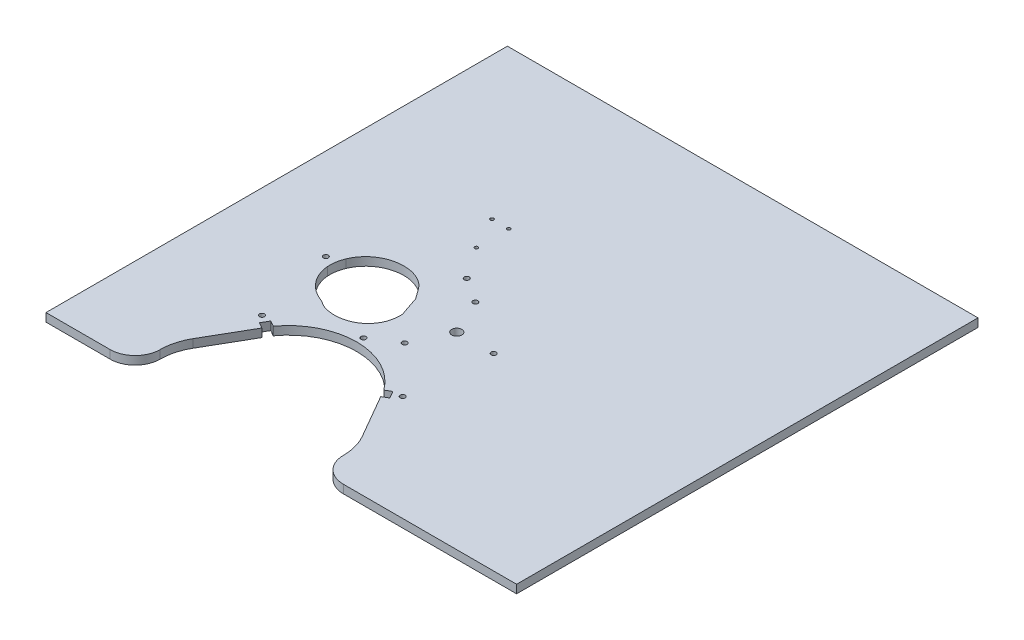
SolidWorks part; units mm, degrees
material "ABS PC"
ref_plane "Plan de face" through (0, 0, 0) normal (0, 0, 1) x (1, 0, 0)
ref_plane "Plan de dessus" through (0, 0, 0) normal (0, 1, 0) x (1, 0, 0)
ref_plane "Plan de droite" through (0, 0, 0) normal (1, 0, 0) x (0, 0, -1)
sketch "Esquisse1" plane through (0, 0, 0) normal (0, 1, 0) x (1, 0, 0)
  line L1 (-140.5, 31.9) -> (141.9979, 31.9)
  line L2 (-140.5, 31.9) -> (-140.5, -245.0829)
  line L3 (-140.5, -245.0829) -> (141.9979, -245.0829)
  line L4 (141.9979, 31.9) -> (141.9979, -245.0829)
  line L5 (38, -245.0829) -> (54.7016, -245.0829) construction
  line L6 (99.5, 31.9) -> (113.5, 31.9) construction
  arc A0 (-32, -23.5) -> (-95.029, -220.3153) centre (-32, -132) ccw construction
extrude "Boss.-Extru.1" add sketch "Esquisse1" along normal blind 5
sketch "Esquisse2" plane through (0, 0, 0) normal (0, 1, 0) x (1, 0, 0)
  line L3 (-65.1815, -184) -> (-68.6457, -182)
  line L4 (-68.6457, -182) -> (-71.1457, -186.3301)
  line L5 (-71.1457, -186.3301) -> (-67.6815, -188.3301)
  line L7 (-32, -132) -> (-32, -245.0829) construction
  line L8 (-65.1815, -184) -> (-67.6815, -188.3301) construction
  line L9 (-62.6323, -132) -> (62.6323, -132) construction
  line L10 (-32, -62.6323) -> (-32, 62.6323) construction
  line L11 (-67.6815, -188.3301) -> (-82.8539, -214.6094)
  line L13 (-65.1815, -184) -> (-61.7174, -186) construction
  line L14 (-32, -168.5125) -> (-32, -231.5125) construction
  line L16 (140.1, -245.0829) -> (-140.1, -245.0829) construction
  line L17 (-140.5, -245.0829) -> (141.9979, -245.0829) construction
  line L18 (1.1815, -184) -> (-2.2826, -186) construction
  line L20 (1.1815, -184) -> (3.6815, -188.3301) construction
  line L21 (3.6815, -188.3301) -> (18.8539, -214.6094)
  line L22 (7.1457, -186.3301) -> (3.6815, -188.3301)
  line L23 (4.6457, -182) -> (7.1457, -186.3301)
  line L24 (1.1815, -184) -> (4.6457, -182)
  line L25 (-69.8957, -184.1651) -> (-74.2258, -181.6651) construction
  line L26 (-102, -245.0829) -> (38, -245.0829)
  arc A1 (1.1815, -184) -> (-65.1815, -184) centre (-32, -208.0829) ccw
  arc A2 (-102, -245.0829) -> (-87, -230.0829) centre (-102, -230.0829) ccw
  arc A3 (-102, -245.0829) -> (-93.2863, -217.8734) centre (-102, -230.0829) ccw construction
  arc A4 (-87, -230.0829) -> (-82.8539, -214.6094) centre (-56.0531, -230.0829) cw
  arc A5 (23, -230.0829) -> (18.8539, -214.6094) centre (-7.9469, -230.0829) ccw
  arc A6 (38, -245.0829) -> (23, -230.0829) centre (38, -230.0829) cw
  circle A8 centre (-74.2258, -181.6651) radius 1.5
  circle A10 centre (10.2258, -181.6651) radius 1.5
  dimension "D4" = 41
  dimension "D8" = 5
  dimension "D9" = 3
  dimension "D1" = 4
  dimension "D2" = 52
  dimension "D3" = 37
  dimension "D5" = 90
  dimension "D6" = 5
  dimension "D7" = 30
extrude "Enlèv. mat.-Extru.2" cut sketch "Esquisse2" along normal through all
sketch "Esquisse3" plane through (0, 5, 0) normal (0, 1, 0) x (1, 0, 0)
  line L0 (-34.1228, -139.1933) -> (-38.0727, -127.5986) construction
  line L1 (-32.6381, -138.8997) -> (-36.7122, -126.9407)
  spline S0 degree 3 poles (622.8385, 1730.6752) (80.7611, -245.6058) (-80.6273, -179.6704) (-78.4184, -133.519) (-78.3402, -132.7796) (-78.0993, -131.3086) (-77.9355, -130.5788) (-42.7423, -7.2308) (1168.5437, -237.6426) (1911.2991, -327.4332) knots -15.02078 -15.02078 -15.02078 -15.02078 0.25 0.25 0.5 0.5 0.75 0.75 43.632511 43.632511 43.632511 43.632511 only from (-78.4282, -136.5) to (-77, -127.755)
  spline S1 degree 3 poles (-2047.8331, 22.2373) (1285.2883, 298.7745) (-111.0384, -8.8099) (-77.7521, -140.3949) (-77.5862, -140.9451) (-77.2098, -142.0199) (-76.9992, -142.5463) (-76.3026, -144.0933) (-75.7516, -145.082) (-74.8018, -146.5043) (-74.4641, -146.9675) (-73.7589, -147.8582) (-73.3897, -148.2875) (-72.6207, -149.1162) (-72.221, -149.5157) (-71.3904, -150.2844) (-70.9598, -150.6538) (-70.0613, -151.3565) (-69.5957, -151.6914) (-68.8865, -152.1695) (-68.6478, -152.325) (-68.1687, -152.6332) (-67.9269, -152.7834) (-67.1868, -153.2096) (-66.681, -153.4729) (-65.648, -153.9633) (-65.1207, -154.1899) (-64.0641, -154.6374) (-63.5349, -154.8594) (-62.7536, -155.2167) (-62.5025, -155.3541) (-50.6518, -163.0047) (-54.4985, -200.5995) (887.4578, 1603.7366) knots -14.73487 -14.73487 -14.73487 -14.73487 0.125 0.125 0.1875 0.1875 0.25 0.25 0.375 0.375 0.4375 0.4375 0.5 0.5 0.5625 0.5625 0.625 0.625 0.6875 0.6875 0.71875 0.71875 0.75 0.75 0.8125 0.8125 0.875 0.875 0.9375 0.9375 0.96875 0.96875 2.47079 2.47079 2.47079 2.47079 only from (-78.4282, -136.5) to (-61.5478, -156)
  spline S2 degree 3 poles (-1745.4139, 892.0598) (133.9741, 43.0874) (-4.0887, -175.9233) (-59.26, -157.2053) (-59.4819, -157.1257) (-59.8129, -157.0004) (-59.9231, -156.9582) (-60.1393, -156.8624) (-60.2451, -156.8096) (-60.557, -156.6406) (-60.7605, -156.5209) (-73.1987, -148.6858) (-65.0496, -108.9252) (-1170.5294, -1819.9055) knots -30.265211 -30.265211 -30.265211 -30.265211 0.5 0.5 0.625 0.625 0.6875 0.6875 0.75 0.75 0.875 0.875 8.537384 8.537384 8.537384 8.537384 only from (-56.3008, -158) to (-61.5478, -156)
  spline S3 degree 3 poles (-1956.1275, 426.9773) (36.5324, -0.0898) (-5.7039, -154.0463) (-51.2435, -158.3269) (-51.8765, -158.3561) (-53.1445, -158.356) (-53.7811, -158.3264) (-125.6227, -151.5571) (-150.9564, 223.9249) (-22.0957, 1838.9163) knots -17.515041 -17.515041 -17.515041 -17.515041 0.25 0.25 0.5 0.5 0.75 0.75 28.888572 28.888572 28.888572 28.888572 only from (-48.7229, -158) to (-56.3008, -158)
  spline S4 degree 3 poles (-1977.7479, 321.8791) (-6.2878, 50.8205) (-0.115, -141.0202) (-98.7511, -175.969) (-241.4243, 33.4773) (1700.8536, 790.126) knots -23.848551 -23.848551 -23.848551 -23.848551 0.5 0.5 28.682267 28.682267 28.682267 28.682267 only from (-43.0995, -156) to (-48.7229, -158)
  spline S5 degree 3 poles (-1413.2384, 1297.5395) (-406.1116, 94.5412) (-96.3939, -196.3537) (-40.3273, -154.1412) (-39.6978, -153.5933) (-38.8098, -152.698) (-38.5222, -152.3857) (-37.972, -151.7435) (-37.7102, -151.4142) (-36.9651, -150.4011) (-36.5206, -149.6933) (-35.9321, -148.5831) (-35.7493, -148.2047) (-35.4099, -147.4317) (-35.253, -147.0364) (-34.8315, -145.8445) (-34.6116, -145.0363) (-34.2836, -143.3948) (-34.1756, -142.5614) (-29.468, -67.9459) (-444.4271, -29.1967) (1924.0799, 241.8608) knots -10.283304 -10.283304 -10.283304 -10.283304 0.125 0.125 0.25 0.25 0.3125 0.3125 0.375 0.375 0.5 0.5 0.5625 0.5625 0.625 0.625 0.75 0.75 0.875 0.875 11.782868 11.782868 11.782868 11.782868 only from (-43.0995, -156) to (-34.1228, -139.1933)
  spline S6 degree 3 poles (-1551.9542, -1429.2656) (-225.4463, -439.24) (5.2747, -190.2243) (-38.7241, -126.6321) (-38.8938, -126.395) (-39.4011, -125.6828) (-39.7418, -125.2097) (-65.8115, -89.2739) (-97.4387, -57.3229) (-1683.4527, -1262.3111) knots -32.920621 -32.920621 -32.920621 -32.920621 0.125 0.125 0.25 0.25 0.5 0.5 19.284457 19.284457 19.284457 19.284457 only from (-38.0727, -127.5986) to (-42.1803, -121.9365)
  spline S7 degree 3 poles (-1585.122, -1394.0623) (-104.6708, -110.2382) (-59.5313, -102.5716) (-23.2166, -142.8993) (-57.0039, -213.0881) (1509.1144, 1139.2237) knots -20.453469 -20.453469 -20.453469 -20.453469 0.5 0.5 26.410068 26.410068 26.410068 26.410068 only from (-44.5252, -119.3729) to (-42.1803, -121.9365)
  spline S8 degree 3 poles (-2016.7995, 207.9698) (-31.3521, -186.0458) (-27.1415, -132.0896) (-45.8045, -118.3724) (-46.1412, -118.1443) (-47.17, -117.4994) (-47.8823, -117.1198) (-49.3548, -116.4512) (-50.1177, -116.1613) (-51.6655, -115.6765) (-52.453, -115.4795) (-54.8487, -115.0237) (-56.4515, -114.9032) (-58.4616, -114.9674) (-58.864, -114.9913) (-59.6694, -115.0612) (-60.0736, -115.1075) (-61.2787, -115.279) (-62.069, -115.4364) (-63.6237, -115.8348) (-64.3882, -116.0762) (-65.8912, -116.6433) (-66.6307, -116.9704) (-68.8015, -118.081) (-70.1374, -118.9698) (-71.9752, -120.5241) (-72.5597, -121.0797) (-73.6682, -122.2715) (-74.1798, -122.8963) (-75.1225, -124.1965) (-75.5545, -124.8718) (-100.0718, -168.7665) (20.7952, -315.4615) (1850.5018, 377.9945) knots -1.71545 -1.71545 -1.71545 -1.71545 0.03125 0.03125 0.0625 0.0625 0.125 0.125 0.1875 0.1875 0.25 0.25 0.375 0.375 0.40625 0.40625 0.4375 0.4375 0.5 0.5 0.5625 0.5625 0.625 0.625 0.75 0.75 0.8125 0.8125 0.875 0.875 0.9375 0.9375 4.786771 4.786771 4.786771 4.786771 only from (-44.5252, -119.3729) to (-77, -127.755)
  spline S9 degree 3 poles (-44.5252, -119.3729) (-44.8276, -119.1086) (-45.1484, -118.8546) (-45.8045, -118.3724) (-46.1412, -118.1443) (-47.17, -117.4994) (-47.8823, -117.1198) (-49.3548, -116.4512) (-50.1177, -116.1613) (-51.6655, -115.6765) (-52.453, -115.4795) (-54.8487, -115.0237) (-56.4515, -114.9032) (-58.4616, -114.9674) (-58.864, -114.9913) (-59.6694, -115.0612) (-60.0736, -115.1075) (-61.2787, -115.279) (-62.069, -115.4364) (-63.6237, -115.8348) (-64.3882, -116.0762) (-65.8912, -116.6433) (-66.6307, -116.9704) (-68.8015, -118.081) (-70.1374, -118.9698) (-71.9752, -120.5241) (-72.5597, -121.0797) (-73.6682, -122.2715) (-74.1798, -122.8963) (-75.1225, -124.1965) (-75.5545, -124.8718) (-76.3379, -126.2745) (-76.6914, -127.0031) (-77, -127.755) knots 0 0 0 0 0.03125 0.03125 0.0625 0.0625 0.125 0.125 0.1875 0.1875 0.25 0.25 0.375 0.375 0.40625 0.40625 0.4375 0.4375 0.5 0.5 0.5625 0.5625 0.625 0.625 0.75 0.75 0.8125 0.8125 0.875 0.875 0.9375 0.9375 1 1 1 1 construction
  spline S10 degree 3 poles (-44.5252, -119.3729) (-44.0857, -119.7569) (-43.6818, -120.1725) (-42.9069, -121.033) (-42.5395, -121.4811) (-42.1803, -121.9365) knots 0 0 0 0 0.5 0.5 1 1 1 1 construction
  spline S11 degree 3 poles (-38.0727, -127.5986) (-38.2306, -127.3537) (-38.3925, -127.1114) (-38.7241, -126.6321) (-38.8938, -126.395) (-39.4011, -125.6828) (-39.7418, -125.2097) (-40.769, -123.7937) (-41.4579, -122.8522) (-42.1803, -121.9365) knots 0 0 0 0 0.125 0.125 0.25 0.25 0.5 0.5 1 1 1 1 construction
  spline S12 degree 3 poles (-43.0995, -156) (-42.36, -155.596) (-41.658, -155.143) (-40.3273, -154.1412) (-39.6978, -153.5933) (-38.8098, -152.698) (-38.5222, -152.3857) (-37.972, -151.7435) (-37.7102, -151.4142) (-36.9651, -150.4011) (-36.5206, -149.6933) (-35.9321, -148.5831) (-35.7493, -148.2047) (-35.4099, -147.4317) (-35.253, -147.0364) (-34.8315, -145.8445) (-34.6116, -145.0363) (-34.2836, -143.3948) (-34.1756, -142.5614) (-34.069, -140.8707) (-34.0707, -140.0299) (-34.1228, -139.1933) knots 0 0 0 0 0.125 0.125 0.25 0.25 0.3125 0.3125 0.375 0.375 0.5 0.5 0.5625 0.5625 0.625 0.625 0.75 0.75 0.875 0.875 1 1 1 1 construction
  spline S13 degree 3 poles (-43.0995, -156) (-43.978, -156.4799) (-44.895, -156.8867) (-46.7726, -157.552) (-47.7397, -157.8128) (-48.7229, -158) knots 0 0 0 0 0.5 0.5 1 1 1 1 construction
  spline S14 degree 3 poles (-48.7229, -158) (-49.3482, -158.1191) (-49.9796, -158.2081) (-51.2435, -158.3269) (-51.8765, -158.3561) (-53.1445, -158.356) (-53.7811, -158.3264) (-55.0464, -158.2072) (-55.6755, -158.1184) (-56.3008, -158) knots 0 0 0 0 0.25 0.25 0.5 0.5 0.75 0.75 1 1 1 1 construction
  spline S15 degree 3 poles (-56.3008, -158) (-57.2287, -157.8243) (-58.1437, -157.584) (-59.26, -157.2053) (-59.4819, -157.1257) (-59.8129, -157.0004) (-59.9231, -156.9582) (-60.1393, -156.8624) (-60.2451, -156.8096) (-60.557, -156.6406) (-60.7605, -156.5209) (-61.1598, -156.2694) (-61.3541, -156.1351) (-61.5478, -156) knots 0 0 0 0 0.5 0.5 0.625 0.625 0.6875 0.6875 0.75 0.75 0.875 0.875 1 1 1 1 construction
  spline S16 degree 3 poles (-78.4282, -136.5) (-78.3481, -137.6268) (-78.1704, -138.7415) (-77.7521, -140.3949) (-77.5862, -140.9451) (-77.2098, -142.0199) (-76.9992, -142.5463) (-76.3026, -144.0933) (-75.7516, -145.082) (-74.8018, -146.5043) (-74.4641, -146.9675) (-73.7589, -147.8582) (-73.3897, -148.2875) (-72.6207, -149.1162) (-72.221, -149.5157) (-71.3904, -150.2844) (-70.9598, -150.6538) (-70.0613, -151.3565) (-69.5957, -151.6914) (-68.8865, -152.1695) (-68.6478, -152.325) (-68.1687, -152.6332) (-67.9269, -152.7834) (-67.1868, -153.2096) (-66.681, -153.4729) (-65.648, -153.9633) (-65.1207, -154.1899) (-64.0641, -154.6374) (-63.5349, -154.8594) (-62.7536, -155.2167) (-62.5025, -155.3541) (-62.0194, -155.6659) (-61.7846, -155.8349) (-61.5478, -156) knots 0 0 0 0 0.125 0.125 0.1875 0.1875 0.25 0.25 0.375 0.375 0.4375 0.4375 0.5 0.5 0.5625 0.5625 0.625 0.625 0.6875 0.6875 0.71875 0.71875 0.75 0.75 0.8125 0.8125 0.875 0.875 0.9375 0.9375 0.96875 0.96875 1 1 1 1 construction
  spline S17 degree 3 poles (-78.4282, -136.5) (-78.4813, -135.7547) (-78.4896, -135.0058) (-78.4184, -133.519) (-78.3402, -132.7796) (-78.0993, -131.3086) (-77.9355, -130.5788) (-77.5276, -129.1489) (-77.2836, -128.446) (-77, -127.755) knots 0 0 0 0 0.25 0.25 0.5 0.5 0.75 0.75 1 1 1 1 construction
  spline S18 degree 1 poles (-36.7122, -126.9407) (-41.0026, -121.0075) knots 0 0 1 1 construction
  spline S19 degree 1 poles (-43.5382, -118.2433) (-41.0026, -121.0075) knots 0 0 1 1 construction
  spline S20 degree 1 poles (-43.5382, -118.2433) (-78.3877, -127.1854) knots 0 0 1 1 construction
  spline S21 degree 1 poles (-79.9245, -136.6065) (-78.3877, -127.1854) knots 0 0 1 1 construction
  spline S22 degree 1 poles (-79.9245, -136.6065) (-62.4058, -157.2304) knots 0 0 1 1 construction
  spline S23 degree 1 poles (-56.58, -159.4738) (-62.4058, -157.2304) knots 0 0 1 1 construction
  spline S24 degree 1 poles (-48.4423, -159.4735) (-56.58, -159.4738) knots 0 0 1 1 construction
  spline S25 degree 1 poles (-42.3803, -157.3164) (-48.4423, -159.4735) knots 0 0 1 1 construction
  spline S26 degree 1 poles (-42.3803, -157.3164) (-32.6381, -138.8997) knots 0 0 1 1 construction
  spline S27 degree 3 poles (-36.7122, -126.9407) (-37.0489, -126.4183) (-37.7663, -125.3811) (-38.8123, -123.9351) (-39.8783, -122.4695) (-40.6231, -121.4886) (-41.0026, -121.0075) knots -0.026313 -0.026313 -0.026313 -0.026313 0.230265 0.486844 0.743422 1 1 1 1
  spline S28 degree 3 poles (-41.0026, -121.0075) (-41.3816, -120.5271) (-41.9595, -119.8249) (-42.8128, -118.9132) (-43.2928, -118.4578) (-43.5382, -118.2433) knots 0 0 0 0 0.5 0.75 1 1 1 1
  spline S29 degree 3 poles (-43.5382, -118.2433) (-44.2085, -117.6576) (-45.668, -116.5984) (-48.7422, -114.9606) (-52.9567, -113.6589) (-58.1012, -113.2676) (-62.4199, -113.8802) (-65.6802, -114.9098) (-68.0602, -115.9614) (-70.3038, -117.2757) (-73.0441, -119.3298) (-75.4514, -121.9172) (-77.2957, -124.8102) (-78.0583, -126.3828) (-78.3877, -127.1854) knots 0 0 0 0 0.0625 0.125 0.25 0.375 0.5 0.5625 0.625 0.6875 0.75 0.875 0.9375 1 1 1 1
  spline S30 degree 3 poles (-78.3877, -127.1854) (-78.9951, -128.6654) (-79.8834, -131.7671) (-80.0383, -135.0072) (-79.9245, -136.6065) knots 0 0 0 0 0.5 1 1 1 1
  spline S31 degree 3 poles (-79.9245, -136.6065) (-79.8381, -137.8205) (-79.4548, -140.2309) (-78.2255, -143.7308) (-76.4515, -146.913) (-74.5447, -149.3162) (-72.8435, -151.0147) (-71.4537, -152.2062) (-70.2003, -153.1018) (-69.2326, -153.7373) (-68.1615, -154.4002) (-66.8138, -155.0929) (-65.4359, -155.6871) (-64.5162, -156.0739) (-64.0145, -156.2923) (-63.4863, -156.5263) (-63.1919, -156.6872) (-62.7662, -156.9764) (-62.5236, -157.1482) (-62.4058, -157.2304) knots 0 0 0 0 0.125 0.25 0.375 0.5 0.5625 0.625 0.6875 0.71875 0.75 0.8125 0.875 0.90625 0.921875 0.9375 0.96875 0.984375 1 1 1 1
  spline S32 degree 3 poles (-62.4058, -157.2304) (-62.3033, -157.3018) (-62.1055, -157.4395) (-61.7597, -157.6676) (-61.4139, -157.8762) (-61.0842, -158.0657) (-60.6317, -158.2936) (-60.2222, -158.4501) (-59.8807, -158.5764) (-59.3978, -158.7449) (-58.7965, -158.9371) (-57.8199, -159.2121) (-57.0779, -159.3795) (-56.58, -159.4738) knots 0 0 0 0 0.0625 0.125 0.1875 0.25 0.3125 0.375 0.4375 0.5 0.625 0.75 1 1 1 1
  spline S33 degree 3 poles (-56.58, -159.4738) (-53.9148, -159.9786) (-51.107, -159.9809) (-48.4423, -159.4735) knots 0 0 0 0 1 1 1 1
  spline S34 degree 3 poles (-48.4423, -159.4735) (-46.3354, -159.0723) (-44.2625, -158.3447) (-42.3803, -157.3164) knots 0 0 0 0 1 1 1 1
  spline S35 degree 3 poles (-42.3803, -157.3164) (-41.5755, -156.8767) (-40.0252, -155.8745) (-37.9613, -154.0691) (-36.1433, -151.9316) (-34.696, -149.5994) (-33.5847, -147.0237) (-32.8836, -144.3638) (-32.6087, -142.077) (-32.5748, -140.4768) (-32.5979, -139.5603) (-32.6243, -139.1214) (-32.6381, -138.8997) knots 0 0 0 0 0.126248 0.252496 0.378744 0.504992 0.63124 0.757488 0.883736 0.94686 0.978422 1.009983 1.009983 1.009983 1.009983
  dimension "D1" = 1.5
extrude "Enlèv. mat.-Extru.3" cut sketch "Esquisse3" against normal through all
sketch "Esquisse4" plane through (0, 5, 0) normal (0, 1, 0) x (1, 0, 0)
  circle A0 centre (-7, -132) radius 3
  arc A1 (-5.4384, -134.5616) -> (-5.4384, -129.4384) centre (-7, -132) ccw construction
extrude "Enlèv. mat.-Extru.4" cut sketch "Esquisse4" against normal through all
sketch "Esquisse5" plane through (0, 0, 0) normal (0, -1, 0) x (1, 0, 0)
  circle A0 centre (-45.1, 82.15) radius 1
  circle A2 centre (-55.2, 62.65) radius 1
  circle A3 centre (-45.1, 62.65) radius 1
  dimension "D1" = 2
extrude "Enlèv. mat.-Extru.5" cut sketch "Esquisse5" against normal through all
sketch "Esquisse6" plane through (0, 5, 0) normal (0, 1, 0) x (1, 0, 0)
  circle A0 centre (-85.6, -132) radius 1.5
  circle A1 centre (-32, -163) radius 1.5
  circle A2 centre (-17.0508, -153.25) radius 1.5
  circle A3 centre (15.1224, -132) radius 1.5
  circle A4 centre (-32, -101) radius 1.5
  circle A5 centre (-17.0508, -110.75) radius 1.5
  dimension "D1" = 3
extrude "Enlèv. mat.-Extru.6" cut sketch "Esquisse6" against normal through all
